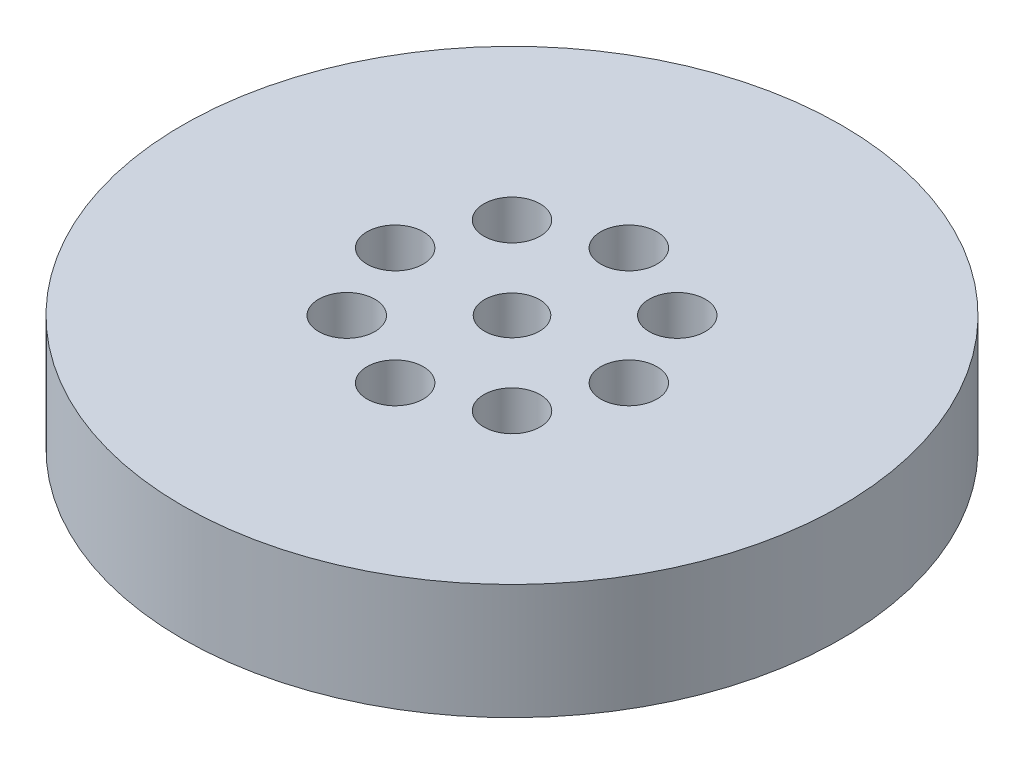
SolidWorks part; units mm, degrees
ref_plane "Front Plane" through (0, 0, 0) normal (0, 0, 1) x (1, 0, 0)
ref_plane "Top Plane" through (0, 0, 0) normal (0, 1, 0) x (1, 0, 0)
ref_plane "Right Plane" through (0, 0, 0) normal (1, 0, 0) x (0, 0, -1)
sketch "Sketch1" plane through (0, 0, 0) normal (0, 1, 0) x (1, 0, 0)
  circle A0 centre (0, 0) radius 60
  dimension "FLANGE_OD" = 120
extrude "Boss-Extrude1" add sketch "Sketch1" along normal blind 21
sketch "Sketch2" plane through (0, 0, 0) normal (0, 1, 0) x (1, 0, 0)
  circle A0 centre (0, 0) radius 5
  dimension "BORE_D" = 10
extrude "Cut-Extrude1" cut sketch "Sketch2" along normal through all
sketch "Sketch3" plane through (0, 21, 0) normal (0, 1, 0) x (1, 0, 0)
  circle A0 centre (0, 0) radius 21.2728 construction
  circle A1 centre (-21.2728, 0) radius 5.1186
  dimension "BOLT_D" = 10.2373
  dimension "BOLT_PCD" = 42.5455
extrude "Cut-Extrude2" cut sketch "Sketch3" against normal blind 18.709
pattern_circular "CirPattern1" count 8 over 360 about axis through (0, 0, 0) along (0, 1, 0) of "Cut-Extrude2"
